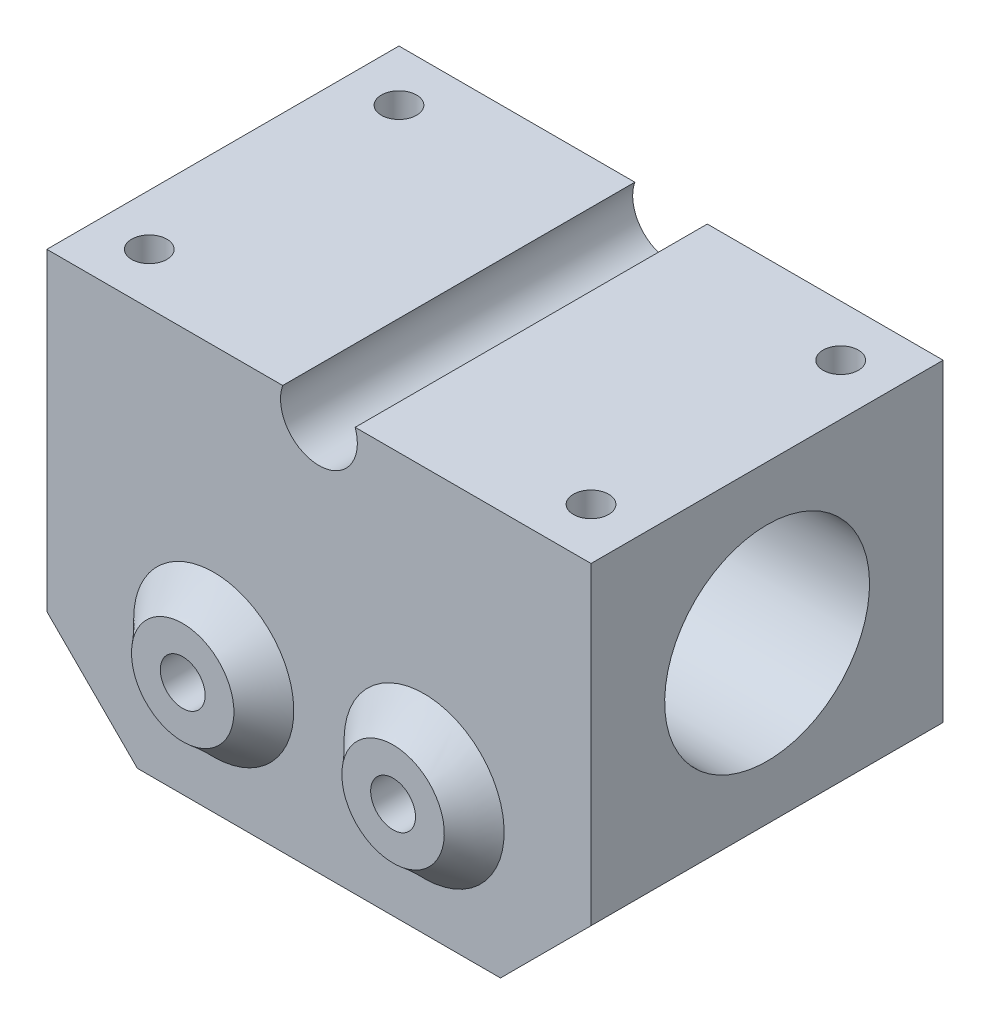
SolidWorks part; units mm, degrees
ref_plane "Ön Düzlem" through (0, 0, 0) normal (0, 0, 1) x (1, 0, 0)
ref_plane "Üst Düzlem" through (0, 0, 0) normal (0, 1, 0) x (1, 0, 0)
ref_plane "Sağ Düzlem" through (0, 0, 0) normal (1, 0, 0) x (0, 0, -1)
sketch "Sketch1" plane through (0, 0, 0) normal (0, 0, 1) x (1, 0, 0)
  line L0 (0, 0) -> (0, -49)
  line L1 (0, -49) -> (-14.1421, -63.1421)
  line L2 (-14.1421, -63.1421) -> (-70.8579, -63.1421)
  line L3 (-42.5, 2.0857) -> (-42.5, -80.6333) construction
  line L4 (0, 0) -> (-85, 0)
  line L5 (-85, -49) -> (-70.8579, -63.1421)
  line L6 (-85, 0) -> (-85, -49)
  point P9 (-42.5, -63.1421)
  point P11 (-42.5, 0)
  dimension "D1" = 49
  dimension "D2" = 20
  dimension "D3" = 135
  dimension "D4" = 42.5
extrude "Boss-Extrude1" add sketch "Sketch1" along normal mid plane 55
sketch "Sketch2" plane through (0, 0, 27.5) normal (0, 0, 1) x (1, 0, 0)
  line L0 (0, 0) -> (-85, 0) construction
  line L1 (-85, 0) -> (-85, -49) construction
  line L2 (-48.1569, 0) -> (-36.8431, 0)
  line L3 (-48.1569, 0) -> (-36.8431, 0)
  arc A0 (-48.1569, 0) -> (-36.8431, 0) centre (-42.5, -2) ccw
  line M1 (0, 0) -> (-85, 0)
  dimension "D2" = 12
  dimension "D1" = 2
  dimension "75/2" = 42.5
extrude "Cut-Extrude1" cut sketch "Sketch2" against normal up to surface (55 mm away) contours A0 M1 region at (-42.5, -3.5067, 27.5) up to face at (-42.5, -37.3807, -27.5)
sketch "Sketch3" plane through (0, 0, 0) normal (1, 0, 0) x (0, 0, -1)
  line L0 (-27.5, 0) -> (27.5, 0) construction
  line L1 (0, -3.1973) -> (0, -39.5378) construction
  line L2 (-10.0056, -35) -> (18.0102, -35) construction
  circle A0 centre (0, -24.5) radius 10.5
  dimension "D1" = 21
  dimension "D2" = 24.5
extrude "Cut-Extrude2" cut sketch "Sketch3" against normal up to surface (85 mm away) up to face at (-85, -24.5, 0)
sketch "Sketch4" plane through (0, 0, 0) normal (1, 0, 0) x (0, 0, -1)
  circle A0 centre (0, -24.5) radius 16
  circle A1 centre (0, -24.5) radius 10.5
  dimension "D1" = 32
  dimension "D2" = 21
extrude "Cut-Extrude3" cut sketch "Sketch4" against normal blind 32.3
sketch "Sketch5" plane through (-85, 0, 0) normal (-1, 0, 0) x (0, 0, 1)
  circle A0 centre (0, -24.5) radius 16
  circle A1 centre (0, -24.5) radius 10.5
  dimension "D1" = 21
  dimension "32" = 32
extrude "Cut-Extrude4" cut sketch "Sketch5" against normal blind 32.3
sketch "Sketch6" plane through (0, 0, 0) normal (0, 1, 0) x (1, 0, 0)
  line L0 (-83.5179, 0) -> (14.1544, 0) construction
  line L1 (-42.5, 28.6455) -> (-42.5, -30.6646) construction
  line L2 (-85, -27.5) -> (-85, 27.5) construction
  line L3 (0, 27.5) -> (-36.8431, 27.5) construction
  line L4 (0, -27.5) -> (0, 27.5) construction
  circle A0 centre (-8, 19.5) radius 2.75
  circle A1 centre (-8, -19.5) radius 2.75
  circle A2 centre (-77, -19.5) radius 2.75
  circle A3 centre (-77, 19.5) radius 2.75
  dimension "D2" = 5.5
  dimension "D1" = 42.5
  dimension "D3" = 8
  dimension "D4" = 8
extrude "Cut-Extrude5" cut sketch "Sketch6" against normal blind 15
sketch "Sketch7" plane through (0, 0, 27.5) normal (0, 0, 1) x (1, 0, 0)
  line L0 (0, -49) -> (0, 0) construction
  line L1 (-70.8579, -63.1421) -> (-14.1421, -63.1421) construction
  circle A1 centre (-26.07, -43.1421) radius 12.5
  dimension "D4" = 25
  dimension "D2" = 26.07
  dimension "D3" = 20
ref_plane "Plane1" through (0, 0, 32.35) normal (0, 0, 1) x (1, 0, 0)
sketch "Sketch8" plane through (0, 0, 32.35) normal (0, 0, 1) x (1, 0, 0)
  circle A0 centre (-26.07, -43.1421) radius 8
  dimension "D1" = 16
loft "Loft1" add profiles "Sketch7", "Sketch8" connector at (-20.9762, -31.7271, 27.5) connector at (-20.6377, -37.2693, 32.35)
sketch "Sketch9" plane through (0, 0, 32.35) normal (0, 0, 1) x (1, 0, 0)
  line L0 (0, -49) -> (0, 0) construction
  line L1 (-70.8579, -63.1421) -> (-14.1421, -63.1421) construction
  circle A0 centre (-26.07, -43.1421) radius 3.5
  dimension "D1" = 7
  dimension "D2" = 26.07
  dimension "D3" = 20
extrude "Cut-Extrude6" cut sketch "Sketch9" against normal blind 15
ref_plane "Plane2" through (-42.5, 0, 0) normal (1, 0, 0) x (0, 0, -1)
mirror "Mirror1" about plane through (-42.5, 0, 0) normal (1, 0, 0) of "Cut-Extrude6", "Loft1"
